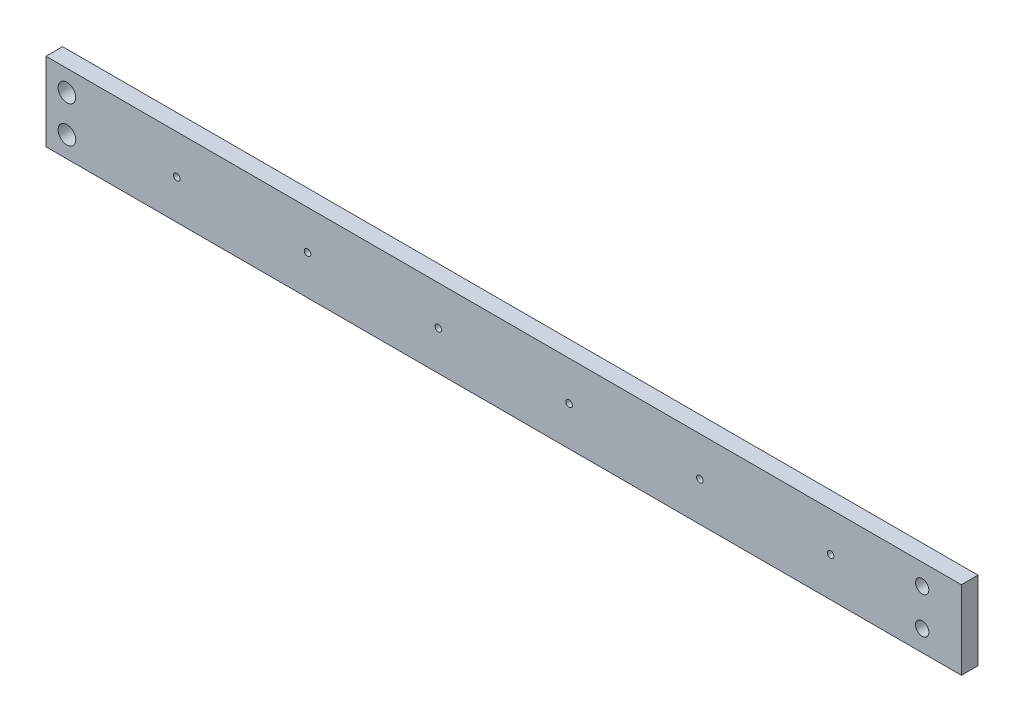
SolidWorks part; units mm, degrees
ref_plane "Front Plane" through (0, 0, 0) normal (0, 0, 1) x (1, 0, 0)
ref_plane "Top Plane" through (0, 0, 0) normal (0, 1, 0) x (1, 0, 0)
ref_plane "Right Plane" through (0, 0, 0) normal (1, 0, 0) x (0, 0, -1)
sketch "Sketch2" plane through (0, 0, 0) normal (0, 0, 1) x (1, 0, 0)
  line L1 (0, 0) -> (350, 0)
  line L2 (0, 0) -> (0, 30)
  line L3 (0, 30) -> (350, 30)
  line L4 (350, 0) -> (350, 30)
  dimension "D1" = 30
  dimension "D2" = 350
extrude "Boss-Extrude1" add sketch "Sketch2" along normal blind 6.35
sketch "Sketch3" plane through (0, 0, 6.35) normal (0, 0, 1) x (1, 0, 0)
  line L0 (8, 30) -> (8, 0) construction
  line L1 (350, 30) -> (0, 30) construction
  line L2 (0, 30) -> (0, 0) construction
  line L3 (0, 0) -> (350, 0) construction
  point P4 (8, 22)
  point P5 (8, 8)
  dimension "D1" = 8
  dimension "D2" = 8
  dimension "D3" = 8
hole_wizard "1/4 Clearance Hole1" positions "Sketch4" profile "Sketch5" hole size "1/4" standard "ANSI Inch" end condition through all
sketch "Sketch4" plane through (0, 0, 6.35) normal (0, 0, 1) x (1, 0, 0)
  point P0 (8, 22)
  point P3 (8, 8)
sketch "Sketch5" plane through (8, 22, 6.35) normal (1, 0, 0) x (0, -1, 0)
  line L0 (0, 0) -> (0, 6.35)
  line L1 (0, 6.35) -> (3.3782, 6.35)
  line L2 (3.3782, 6.35) -> (3.3782, 0)
  line L5 (3.3782, 0) -> (0, 0)
  line L11 (0, -6.35) -> (0, 107.95) construction
  dimension "Thru Hole Dia." = 6.7564
  dimension "Thru Hole Depth" = 6.35
sketch "Sketch6" plane through (0, 0, 6.35) normal (0, 0, 1) x (1, 0, 0)
  line L0 (0, 15) -> (350, 15) construction
  line L1 (0, 30) -> (0, 0) construction
  line L2 (350, 0) -> (350, 30) construction
  point P6 (50, 15)
  dimension "D1" = 50
hole_wizard "Tap Drill for M3x0.5 Tap1" positions "Sketch6" profile "Sketch7" hole size "M3x0.5" standard "ANSI Metric" end condition through all
sketch "Sketch7" plane through (50, 15, 6.35) normal (1, 0, 0) x (0, -1, 0)
  line L0 (0, 0) -> (0, 6.35)
  line L1 (0, 6.35) -> (1.25, 6.35)
  line L2 (1.25, 6.35) -> (1.25, 0)
  line L5 (1.25, 0) -> (0, 0)
  line L11 (0, -6.35) -> (0, 107.95) construction
  dimension "Thru Hole Dia." = 2.5
  dimension "Thru Hole Depth" = 6.35
pattern_linear "LPattern1" count 6 spacing 50 along (1, 0, 0) of "Tap Drill for M3x0.5 Tap1"
sketch "Sketch8" plane through (0, 0, 0) normal (0, 0, -1) x (-1, 0, 0)
  line L0 (-335, 30) -> (-335, 0) construction
  line L1 (-350, 30) -> (0, 30) construction
  line L2 (0, 0) -> (-350, 0) construction
  line L3 (-350, 0) -> (-350, 30) construction
  point P6 (-335, 15)
  point P7 (-335, 22)
  point P8 (-335, 8)
  point P11 (0, 0)
  dimension "D1" = 15
  dimension "D2" = 7
  dimension "D3" = 7
hole_wizard "Tap Drill for 1/4-20 Tap1" positions "Sketch11" profile "Sketch12" hole size "1/4-20" standard "ANSI Inch" end condition through all
sketch "Sketch11" plane through (0, 0, 0) normal (0, 0, -1) x (-1, 0, 0)
  point P0 (-335, 22)
  point P3 (-335, 8)
sketch "Sketch12" plane through (335, 22, 0) normal (1, 0, 0) x (0, 1, 0)
  line L0 (0, 0) -> (0, 6.35)
  line L1 (0, 6.35) -> (2.5527, 6.35)
  line L2 (2.5527, 6.35) -> (2.5527, 0)
  line L5 (2.5527, 0) -> (0, 0)
  line L11 (0, -6.35) -> (0, 107.95) construction
  dimension "Thru Hole Dia." = 5.1054
  dimension "Thru Hole Depth" = 6.35
